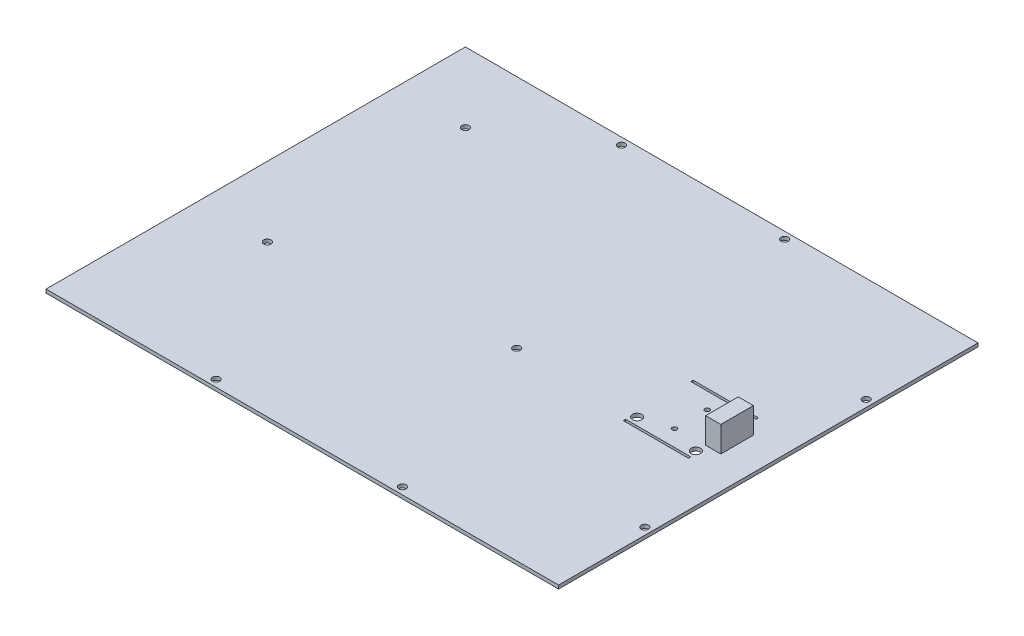
SolidWorks part; units mm, degrees
ref_plane "Front Plane" through (0, 0, 0) normal (0, 0, 1) x (1, 0, 0)
ref_plane "Top Plane" through (0, 0, 0) normal (0, 1, 0) x (1, 0, 0)
ref_plane "Right Plane" through (0, 0, 0) normal (1, 0, 0) x (0, 0, -1)
sketch "Sketch1" plane through (0, 0, 0) normal (0, 1, 0) x (1, 0, 0)
  line L0 (0, 0) -> (220, 0)
  line L1 (0, 0) -> (0, 180)
  line L2 (220, 0) -> (220, 180)
  line L3 (0, 180) -> (220, 180)
  line L4 (0, 90) -> (220, 90) construction
  line L5 (110, 180) -> (110, 0) construction
  line L6 (30, 177) -> (217, 177) construction
  line L7 (30, 177) -> (30, 3) construction
  line L8 (217, 177) -> (217, 3) construction
  line L9 (30, 3) -> (217, 3) construction
  line L10 (30, 150) -> (217, 150) construction
  line L11 (217, 65) -> (30, 65) construction
  circle A0 centre (70, 177) radius 1.55
  circle A1 centre (140, 177) radius 1.55
  circle A2 centre (30, 150) radius 1.55
  circle A3 centre (30, 65) radius 1.55
  circle A4 centre (217, 40) radius 1.55
  circle A5 centre (217, 135) radius 1.55
  circle A6 centre (70, 3) radius 1.55
  circle A7 centre (150, 3) radius 1.55
  circle A8 centre (123, 79) radius 1.55
  dimension "D7" = 3.1
  dimension "D8" = 3.1
  dimension "D9" = 3.1
  dimension "D10" = 3.1
  dimension "D11" = 3.1
  dimension "D12" = 3.1
  dimension "D13" = 3.1
  dimension "D14" = 3.1
  dimension "D15" = 30
  dimension "D20" = 40
  dimension "D18" = 70
  dimension "D21" = 70
  dimension "D22" = 80
  dimension "D23" = 3.1
  dimension "D24" = 123
  dimension "D25" = 79
  dimension "D1" = 180
  dimension "D2" = 220
  dimension "D3" = 3
  dimension "D4" = 30
  dimension "D5" = 3
  dimension "D6" = 3
  dimension "D16" = 65
  dimension "D17" = 70
  dimension "D19" = 45
extrude "Boss-Extrude1" add sketch "Sketch1" along normal blind 1.5
ref_plane "Z" through (0, 0, -90) normal (0, 0, 1) x (1, 0, 0)
ref_plane "X" through (110, 0, 0) normal (-1, 0, 0) x (0, 0, 1)
sketch "Эскиз1" plane through (0, 1.5, 0) normal (0, 1, 0) x (1, 0, 0)
  line L0 (202.75, 104) -> (202.75, 76) construction
  line L1 (202.75, 104) -> (202.75, 76) construction
  line L2 (200.75, 74) -> (172.75, 74) construction
  line L3 (200.75, 74) -> (172.75, 74) construction
  line L4 (204.75, 74) -> (204.75, 106)
  line L5 (202.75, 108) -> (170.75, 108)
  line L6 (168.75, 106) -> (168.75, 74)
  line L7 (170.75, 72) -> (202.75, 72)
  line L8 (204.75, 74) -> (204.75, 106) construction
  line L9 (202.75, 108) -> (170.75, 108) construction
  line L10 (168.75, 106) -> (168.75, 74) construction
  line L11 (170.75, 72) -> (202.75, 72) construction
  line L12 (172.75, 106) -> (200.75, 106) construction
  line L13 (172.75, 106) -> (200.75, 106) construction
  line L14 (170.75, 104) -> (170.75, 76) construction
  line L15 (186.75, 72) -> (186.75, 108) construction
  line L16 (172.75, 75) -> (172.75, 76)
  line L17 (172.75, 75) -> (200.75, 75)
  line L18 (172.75, 76) -> (200.75, 76)
  line L19 (200.75, 75) -> (200.75, 76)
  line L20 (168.75, 90) -> (204.75, 90) construction
  line L21 (200.75, 105) -> (200.75, 104)
  line L22 (172.75, 105) -> (200.75, 105)
  line L23 (172.75, 105) -> (172.75, 104)
  line L24 (172.75, 104) -> (200.75, 104)
  line L26 (187, 108) -> (187, 74) construction
  line L27 (0, 180) -> (0, 0) construction
  line L28 (220, 180) -> (0, 180) construction
  arc A0 (202.75, 104) -> (200.75, 106) centre (200.75, 104) ccw construction
  arc A1 (202.75, 104) -> (200.75, 106) centre (200.75, 104) ccw construction
  arc A2 (200.75, 74) -> (202.75, 76) centre (200.75, 76) ccw construction
  arc A3 (200.75, 74) -> (202.75, 76) centre (200.75, 76) ccw construction
  arc A4 (204.75, 106) -> (202.75, 108) centre (202.75, 106) ccw
  arc A5 (170.75, 108) -> (168.75, 106) centre (170.75, 106) ccw
  arc A6 (168.75, 74) -> (170.75, 72) centre (170.75, 74) ccw
  arc A7 (202.75, 72) -> (204.75, 74) centre (202.75, 74) ccw
  arc A8 (204.75, 106) -> (202.75, 108) centre (202.75, 106) ccw construction
  arc A9 (170.75, 108) -> (168.75, 106) centre (170.75, 106) ccw construction
  arc A10 (168.75, 74) -> (170.75, 72) centre (170.75, 74) ccw construction
  arc A11 (202.75, 72) -> (204.75, 74) centre (202.75, 74) ccw construction
  arc A12 (172.75, 74) -> (170.75, 76) centre (172.75, 76) cw construction
  arc A13 (170.75, 104) -> (172.75, 106) centre (172.75, 104) cw construction
  circle A14 centre (186.75, 83) radius 1
  circle A15 centre (186.75, 97) radius 1
  circle A17 centre (199.6, 79.3) radius 2
  circle A18 centre (199.6, 100.7) radius 2
  circle A19 centre (174.4, 79.3) radius 2
  dimension "D6" = 7
  dimension "D7" = 2
  dimension "D8" = 12.6
  dimension "D10" = 4
  dimension "D11" = 12.6
  dimension "D12" = 10.7
  dimension "D14" = 4
  dimension "D16" = 10.7
  dimension "D2" = 2
  dimension "D3" = 1
  dimension "D4" = 2
  dimension "D5" = 2
  dimension "D9" = 10.7
  dimension "D13" = 187
  dimension "D15" = 90
  dimension "D1" = 0
extrude "Вырез-Вытянуть1" cut sketch "Эскиз1" against normal through all
sketch "Sketch2" plane through (0, 1.5, 0) normal (0, 1, 0) x (1, 0, 0)
  line L0 (0, 138) -> (119.3, 138) construction
  line L1 (0, 138) -> (0, 72) construction
  line L2 (119.3, 138) -> (119.3, 72) construction
  line L3 (0, 72) -> (119.3, 72) construction
  line L4 (0, 180) -> (0, 0) construction
  line L5 (220, 180) -> (0, 180) construction
  line L6 (85.48, 131.67) -> (85.48, 72) construction
  circle A0 centre (85.48, 131.67) radius 1
  circle A1 centre (85.48, 80.87) radius 1
  dimension "D4" = 33.82
  dimension "D5" = 6.33
  dimension "D6" = 2
  dimension "D7" = 50.8
  dimension "D8" = 2
  dimension "D1" = 42
  dimension "D2" = 66
  dimension "D3" = 119.3
sketch "Sketch3" plane through (0, 1.5, 0) normal (0, 1, 0) x (1, 0, 0)
  line L0 (199.6, 83.5) -> (199.6, 97.5)
  line L1 (199.6, 83.5) -> (206.1, 83.5)
  line L2 (199.6, 97.5) -> (206.1, 97.5)
  line L3 (206.1, 83.5) -> (206.1, 97.5)
  line L4 (186.75, 76) -> (186.75, 105) construction
  line L5 (200.75, 76) -> (172.75, 76) construction
  line L6 (200.75, 105) -> (172.75, 105) construction
  line L7 (186.75, 90.5) -> (206.1, 90.5) construction
  line L8 (199.6, 90.5) -> (206.1, 90.5) construction
  line L9 (199.6, 79.3) -> (199.6, 100.7) construction
  dimension "D1" = 6.5
  dimension "D2" = 14
extrude "Boss-Extrude2" add sketch "Sketch3" along normal blind 11
